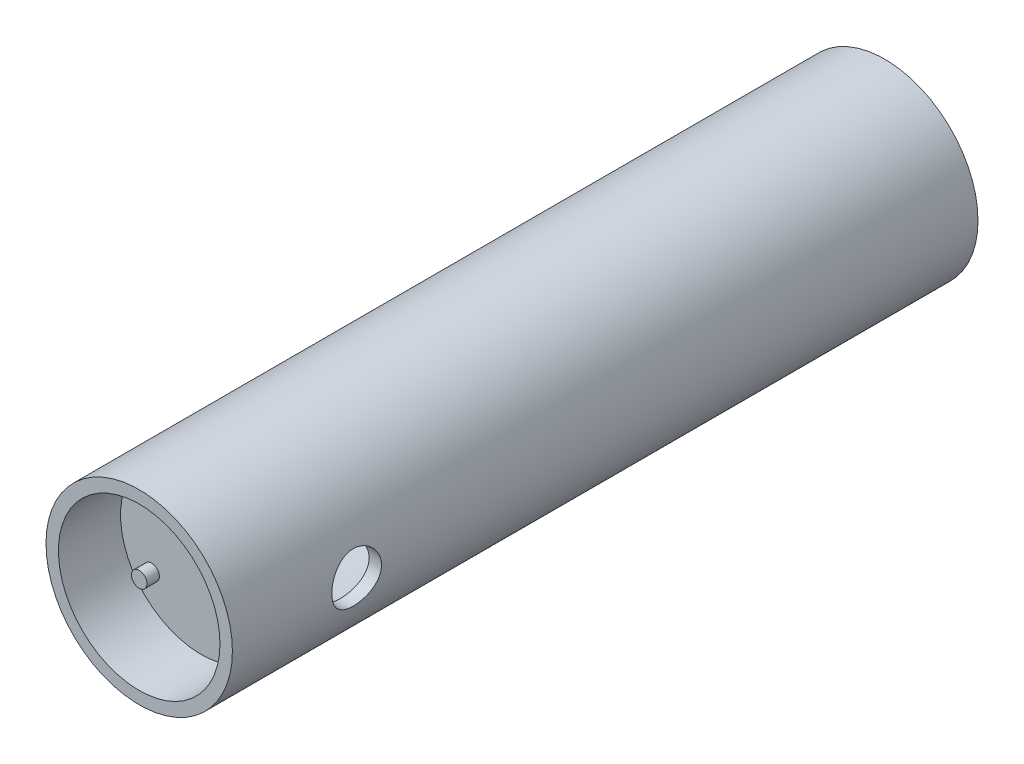
SolidWorks part; units mm, degrees
ref_plane "Plano frontal" through (0, 0, 0) normal (0, 0, 1) x (1, 0, 0)
ref_plane "Plano superior" through (0, 0, 0) normal (0, 1, 0) x (1, 0, 0)
ref_plane "Plano direito" through (0, 0, 0) normal (1, 0, 0) x (0, 0, -1)
sketch "Esboço1" plane through (0, 0, 0) normal (1, 0, 0) x (0, 0, -1)
  line L0 (-60, 0) -> (60, 0)
  line L4 (-60, 0) -> (-60, 15)
  line L5 (-60, 15) -> (60, 15)
  line L6 (60, 15) -> (60, 0)
  point P4 (0, 0)
  dimension "D1" = 120
  dimension "D3" = 15
revolve "Revolução1" add sketch "Esboço1" angle 360 about L0
sketch "Esboço2" plane through (0, 0, 60) normal (0, 0, 1) x (1, 0, 0)
  circle A0 centre (0, 0) radius 13
  dimension "D1" = 26
extrude "Corte-extrusão1" cut sketch "Esboço2" against normal through all
ref_plane "Plano1" through (0, 0, 50) normal (0, 0, 1) x (1, 0, 0)
sketch "Esboço3" plane through (0, 0, 50) normal (0, 0, 1) x (1, 0, 0)
  circle A0 centre (0, 0) radius 13
  point P0 (0, 0)
  point P1 (0, 0)
  dimension "D1" = 26
extrude "Ressalto-extrusão1" add sketch "Esboço3" against normal blind 5 separate body
sketch "Esboço4" plane through (0, 0, 50) normal (0, 0, 1) x (1, 0, 0)
  line L1 (10, -7.5) -> (-10, -7.5) construction
  line L2 (10, -7.5) -> (10, 7.5) construction
  line L3 (10, 7.5) -> (-10, 7.5) construction
  line L4 (-10, -7.5) -> (-10, 7.5) construction
  line L5 (10, -7.5) -> (-10, 7.5) construction
  line L6 (10, 7.5) -> (-10, -7.5) construction
  circle A0 centre (-8, -5.5) radius 1.25
  circle A1 centre (8, -5.5) radius 1.25
  point P0 (0, 0)
  point P10 (0, 0)
  dimension "D5" = 2.5
  dimension "D6" = 2
  dimension "D1" = 20
  dimension "D2" = 15
  dimension "D3" = 2
  dimension "D4" = 2
extrude "Ressalto-extrusão2" add sketch "Esboço4" along normal blind 2
sketch "Esboço5" plane through (0, 0, 50) normal (0, 0, 1) x (1, 0, 0)
  line L0 (-10, 4.5) -> (10, 4.5)
  line L2 (10, 4.5) -> (10, 7.5)
  line L3 (10, 7.5) -> (-10, 7.5)
  line L4 (-10, 4.5) -> (-10, 7.5)
  point P0 (0, 0)
  dimension "D1" = 20
  dimension "D2" = 4.5
  dimension "D3" = 3
  dimension "D4" = 10
extrude "Corte-extrusão2" cut sketch "Esboço5" against normal up to next
sketch "Esboço6" plane through (0, 0, 0) normal (1, 0, 0) x (0, 0, -1)
  line L0 (0, 0) -> (-60, 0) construction
  line L1 (-60, 15) -> (-60, -15) construction
  circle A0 centre (-40, 0) radius 4
  dimension "D2" = 8
  dimension "D1" = 20
extrude "Corte-extrusão3" cut sketch "Esboço6" against normal through all both and the other way through all
